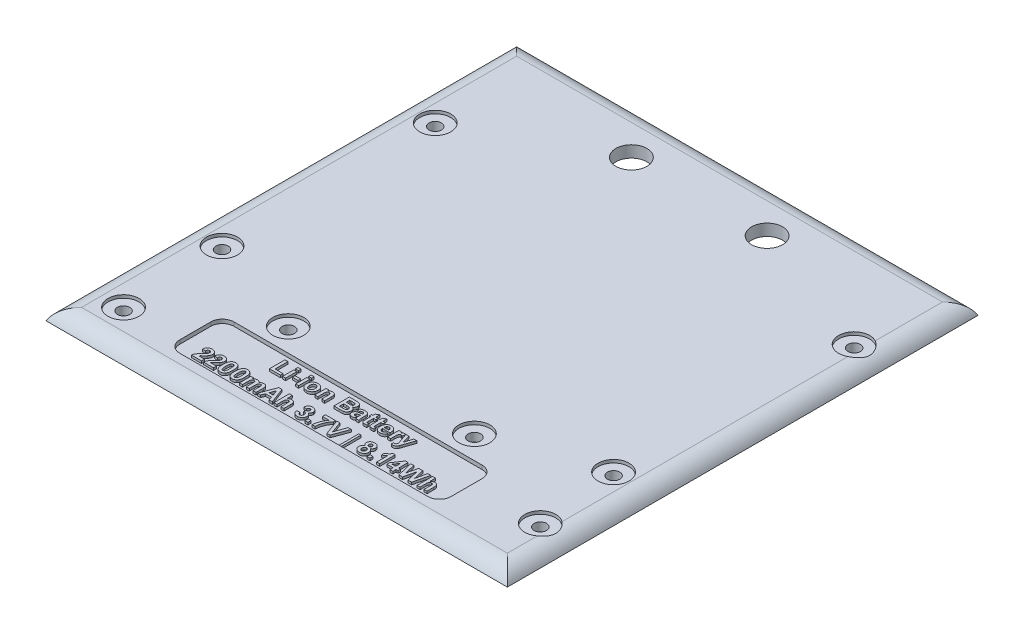
SolidWorks part; units mm, degrees
ref_plane "前视基准面" through (0, 0, 0) normal (0, 0, 1) x (1, 0, 0)
ref_plane "上视基准面" through (0, 0, 0) normal (0, 1, 0) x (1, 0, 0)
ref_plane "右视基准面" through (0, 0, 0) normal (1, 0, 0) x (0, 0, -1)
other "Configuration Table"
sketch "草图1" plane through (0, 0, 0) normal (0, 1, 0) x (1, 0, 0)
  line L0 (0, 0) -> (0, -55) construction
  line L1 (26.5, -64.4) -> (74.5, -64.4) construction
  line L2 (33, 17.6) -> (68, 17.6) construction
  line L3 (-9, 30) -> (110, 30)
  line L4 (-9, 30) -> (-9, -91.4)
  line L5 (-9, -91.4) -> (110, -91.4)
  line L6 (110, 30) -> (110, -91.4)
  circle A0 centre (0, 0) radius 1.6
  circle A1 centre (0, -55) radius 1.6
  circle A2 centre (26.5, -64.4) radius 1.6
  circle A3 centre (74.5, -64.4) radius 1.6
  circle A4 centre (101, -55) radius 1.6
  circle A5 centre (103.5, 4.55) radius 1.6
  circle A6 centre (33, 17.6) radius 4
  circle A7 centre (68, 17.6) radius 4
  circle A8 centre (103, -75.9) radius 1.6
  dimension "D1" = 3.2
  dimension "D2" = 55
  dimension "D3" = 9.4
  dimension "D6" = 26.5
  dimension "D7" = 2.5
  dimension "D8" = 59.55
  dimension "D10" = 6.5
  dimension "D11" = 30
  dimension "D13" = 35
  dimension "D14" = 33
  dimension "D15" = 17.6
  dimension "D16" = 8
  dimension "D17" = 20.9
  dimension "D18" = 2
  dimension "D19" = 3.2
  dimension "D4" = 26.5
  dimension "D5" = 48
  dimension "D9" = 9
  dimension "D12" = 27
extrude "凸台-拉伸1" add sketch "草图1" along normal blind 3
sketch "草图2" plane through (-9, 0, 0) normal (-1, 0, 0) x (0, 0, 1)
  line L0 (-30, 3) -> (91.4, 3) construction
  line L1 (-30, 0) -> (-30, 3)
  line L2 (-30, 3) -> (-25.4174, 3)
  line L3 (86.8174, 3) -> (91.4, 3)
  line L4 (91.4, 3) -> (91.4, 0)
  arc A0 (-25.4174, 3) -> (-30, 0) centre (-25.4174, -2) ccw
  arc A1 (91.4, 0) -> (86.8174, 3) centre (86.8174, -2) ccw
  dimension "D1" = 10
  dimension "D2" = 10
extrude "切除-拉伸1" cut sketch "草图2" against normal through all
sketch "草图3" plane through (0, 0, 0) normal (0, 0, 1) x (1, 0, 0)
  line L0 (50.5, 3) -> (50.5, 0) construction
  line L1 (110, 3) -> (-9, 3) construction
  line L2 (-9, 0) -> (110, 0) construction
  line L3 (-9, 0) -> (-9, 3)
  line L4 (-9, 3) -> (-4.4174, 3)
  line L5 (110, 3) -> (105.4174, 3)
  line L6 (110, 0) -> (110, 3)
  arc A0 (-4.4174, 3) -> (-9, 0) centre (-4.4174, -2) ccw
  arc A1 (105.4174, 3) -> (110, 0) centre (105.4174, -2) cw
  point P1 (-9, 0)
  point P12 (0, 0)
  dimension "D1" = 10
extrude "切除-拉伸2" cut sketch "草图3" against normal through all and the other way through all
sketch "草图4" plane through (0, 0, 0) normal (1, 0, 0) x (0, 0, -1)
  line L0 (-91.4, 0) -> (30, 0) construction
  line L1 (-88.9, 0) -> (-88.9, -7.401)
  line L2 (-88.9, 0) -> (-81.499, 0)
  circle A0 centre (-76.4, -12.5) radius 12.5 construction
  arc A1 (-81.499, 0) -> (-88.9, -7.401) centre (-76.4, -12.5) ccw
  circle A2 centre (-76.4, -12.5) radius 13.5 construction
  dimension "D1" = 25
  dimension "D2" = 15
  dimension "D3" = 1
  dimension "D5" = 2.5
extrude "凸台-拉伸2" add sketch "草图4" along normal through all and the other way through all
sketch "草图5" plane through (0, 0, 0) normal (0, -1, 0) x (1, 0, 0)
  line L0 (110, 81.499) -> (-9, 81.499) construction
  line L1 (-5, 81.499) -> (-9, 81.499)
  line L2 (-5, 81.499) -> (-5, 88.9)
  line L3 (-5, 88.9) -> (-9, 88.9)
  line L4 (-9, 81.499) -> (-9, 88.9)
  line L5 (110, 88.9) -> (-9, 88.9) construction
  line L6 (110, 81.499) -> (95, 81.499)
  line L7 (110, 81.499) -> (110, 88.9)
  line L8 (110, 88.9) -> (95, 88.9)
  line L9 (95, 81.499) -> (95, 88.9)
  dimension "D1" = 4
  dimension "D2" = 15
extrude "切除-拉伸3" cut sketch "草图5" along normal through all
sketch "草图6" plane through (0, 0, 0) normal (0, -1, 0) x (1, 0, 0)
  line L1 (95, 88.9) -> (92, 88.9)
  line L2 (95, 88.9) -> (95, 73.9)
  line L3 (95, 73.9) -> (92, 73.9)
  line L4 (92, 88.9) -> (92, 73.9)
  line L5 (-5, 88.9) -> (7, 88.9)
  line L6 (-5, 88.9) -> (-5, 74.9)
  line L7 (-5, 74.9) -> (7, 74.9)
  line L8 (7, 88.9) -> (7, 74.9)
  dimension "D1" = 3
  dimension "D2" = 15
  dimension "D3" = 14
  dimension "D4" = 12
extrude "凸台-拉伸3" add sketch "草图6" along normal blind 5
fillet "圆角1" radius 10 1 edges at (93.5, -5, 87.625)
sketch "草图8" plane through (0, -5, 0) normal (0, -1, 0) x (1, 0, 0)
  line L1 (-5, 88.9) -> (7, 88.9)
  line L2 (-5, 88.9) -> (-5, 74.9)
  line L3 (-5, 74.9) -> (7, 74.9)
  line L4 (7, 88.9) -> (7, 74.9)
extrude "凸台-拉伸4" add sketch "草图8" along normal blind 10
sketch "草图9" plane through (-5, 0, 0) normal (-1, 0, 0) x (0, 0, 1)
  line L1 (88.9, -15) -> (88.9, 0) construction
  line L2 (88.9, -15) -> (74.9, -15) construction
  circle A0 centre (83.9, -10) radius 2.05
  dimension "D1" = 4.1
  dimension "D2" = 5
  dimension "D3" = 5
extrude "切除-拉伸4" cut sketch "草图9" against normal blind 5
sketch "草图10" plane through (7, 0, 0) normal (1, 0, 0) x (0, 0, -1)
  line L0 (-88.9, -15) -> (-80.4, -23.5)
  line L1 (-74.9, -23.5) -> (-74.9, -15)
  line L2 (-74.9, -15) -> (-88.9, -15) construction
  line L3 (-74.9, -15) -> (-88.9, -15)
  line L4 (-80.4, -23.5) -> (-74.9, -23.5)
  dimension "D1" = 45
  dimension "D2" = 5.5
extrude "凸台-拉伸5" add sketch "草图10" against normal up to surface (12 mm away) up to face at (-5, -10, 85.95)
sketch "草图11" plane through (0, -51.95, 51.95) normal (0, -0.7071, 0.7071) x (1, 0, 0)
  line L0 (7, 52.2552) -> (-5, 52.2552) construction
  line L1 (1, 52.2552) -> (1, 46.2552) construction
  circle A0 centre (1, 46.2552) radius 2.05
  dimension "D1" = 6
  dimension "D2" = 4.1
extrude "切除-拉伸5" cut sketch "草图11" against normal blind 7
fillet "圆角2" radius 5 1 edges at (1, 0, 74.9)
fillet "圆角3" radius 5 1 edges at (93.5, 0, 73.9)
sketch "草图13" plane through (0, 0, 0) normal (0, -1, 0) x (1, 0, 0)
  line L0 (-5, 69.9) -> (-5, 88.9) construction
  line L1 (-5, 68.9) -> (95, 68.9)
  line L2 (-5, 68.9) -> (-5, 88.9)
  line L3 (-5, 88.9) -> (95, 88.9)
  line L4 (95, 68.9) -> (95, 88.9)
  line L5 (-5, 88.9) -> (-5, 80.4) construction
  point P4 (-5, 88.9)
  point P11 (95, 68.9)
extrude "切除-拉伸7" cut sketch "草图13" along normal through all
sketch "草图14" plane through (0, 0, 0) normal (0, -1, 0) x (1, 0, 0)
  line L0 (-9, 91.4) -> (110, 91.4) construction
  line L1 (-9, -30) -> (-9, 91.4) construction
  circle A0 centre (1, 81.4) radius 1.6
  dimension "D1" = 3.2
  dimension "D2" = 10
  dimension "D3" = 10
extrude "切除-拉伸8" cut sketch "草图14" against normal through all
sketch "草图15" plane through (0, 0, 0) normal (0, -1, 0) x (1, 0, 0)
  line L0 (101, 55) -> (101, 35) construction
  line L1 (0, 55) -> (0, 35) construction
  line L2 (0, 35) -> (101, 35) construction
  circle A0 centre (101, 35) radius 4
  circle A1 centre (0, 35) radius 4
  circle A2 centre (103.5, 17.95) radius 4
  dimension "D1" = 8
  dimension "D3" = 17.05
  dimension "D4" = 2.5
  dimension "D2" = 20
extrude "切除-拉伸9" cut sketch "草图15" against normal blind 1
sketch "草图12" plane through (0, 3, 0) normal (0, 1, 0) x (1, 0, 0)
  circle A0 centre (0, 0) radius 4
  circle A1 centre (0, -55) radius 4
  circle A2 centre (26.5, -64.4) radius 4
  circle A3 centre (74.5, -64.4) radius 4
  circle A4 centre (101, -55) radius 4
  circle A5 centre (103, -75.9) radius 4
  circle A6 centre (103.5, 4.55) radius 4
  circle A7 centre (1, -81.4) radius 4
  dimension "D1" = 8
extrude "切除-拉伸6" cut sketch "草图12" against normal blind 0.8
sketch "草图16" plane through (0, 3, 0) normal (0, 1, 0) x (1, 0, 0)
  line L0 (-9, -91.4) -> (110, -91.4) construction
  line L1 (18.5, -70.4) -> (82.5, -70.4)
  line L2 (15.5, -73.4) -> (15.5, -81.4)
  line L3 (18.5, -84.4) -> (82.5, -84.4)
  line L4 (85.5, -73.4) -> (85.5, -81.4)
  line L5 (50.5, 30) -> (50.5, -91.4) construction
  line L6 (110, 30) -> (-9, 30) construction
  arc A0 (82.5, -70.4) -> (85.5, -73.4) centre (82.5, -73.4) cw
  arc A1 (85.5, -81.4) -> (82.5, -84.4) centre (82.5, -81.4) cw
  arc A2 (18.5, -84.4) -> (15.5, -81.4) centre (18.5, -81.4) cw
  arc A3 (15.5, -73.4) -> (18.5, -70.4) centre (18.5, -73.4) cw
  point P12 (85.5, -70.4)
  point P15 (85.5, -84.4)
  point P18 (15.5, -84.4)
  dimension "D4" = 3
  dimension "D1" = 7
  dimension "D2" = 70
  dimension "D3" = 14
extrude "切除-拉伸10" cut sketch "草图16" against normal blind 1
sketch "草图17" plane through (0, 2, 0) normal (0, 1, 0) x (1, 0, 0)
  line L0 (15.5, -82.9) -> (85.5, -82.9) construction
  line L1 (15.5, -73.4) -> (15.5, -81.4) construction
  line L2 (85.5, -81.4) -> (85.5, -73.4) construction
  line L3 (18.5, -84.4) -> (82.5, -84.4) construction
  line L4 (15.5, -75.9) -> (85.5, -75.9) construction
  line L5 (85.5, -81.4) -> (85.5, -73.4) construction
  text T0 "2200mAh 3.7V | 8.14Wh" font "Arial" height 4
  text T1 "Li-ion Battery" font "Arial" height 4
  dimension "D1" = 1.5
  dimension "D2" = 8.5
extrude "凸台-拉伸6" add sketch "草图17" along normal blind 0.6
